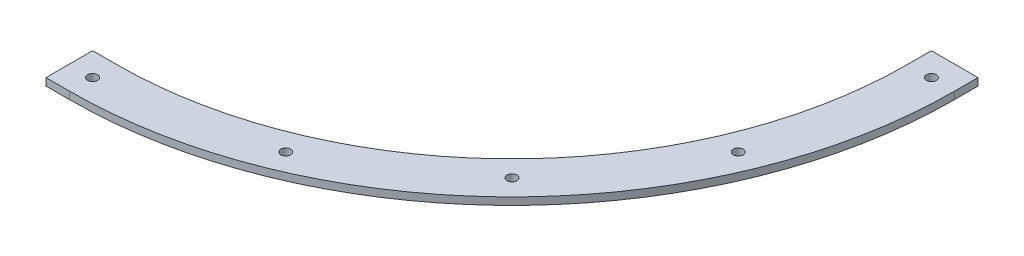
SolidWorks part; units mm, degrees
ref_plane "Front Plane" through (0, 0, 0) normal (0, 0, 1) x (1, 0, 0)
ref_plane "Top Plane" through (0, 0, 0) normal (0, 1, 0) x (1, 0, 0)
ref_plane "Right Plane" through (0, 0, 0) normal (1, 0, 0) x (0, 0, -1)
sketch "Sketch1" plane through (0, 0, 0) normal (0, 1, 0) x (1, 0, 0)
  line L0 (0, -280) -> (100, -280)
  line L1 (100, -280) -> (100, -209.6016)
  line L2 (280, -100) -> (209.6016, -100)
  line L3 (0, 0) -> (0, -280) construction
  line L4 (280, 0) -> (280, -100)
  line L5 (-280, 280) -> (280, 280) construction
  line L6 (-280, 280) -> (-280, -280) construction
  line L7 (-280, -280) -> (280, -280) construction
  line L8 (280, 280) -> (280, -280) construction
  line L9 (-280, 280) -> (280, -280) construction
  line L10 (-280, -280) -> (280, 280) construction
  line L11 (100, -209.6016) -> (209.6016, -100)
  line L12 (-280, 0) -> (-280, -100)
  line L13 (-280, -100) -> (-209.6016, -100)
  line L14 (-209.6016, -100) -> (-100, -209.6016)
  line L15 (-100, -280) -> (-100, -209.6016)
  line L16 (0, -280) -> (-100, -280)
  line L17 (0, 280) -> (-100, 280)
  line L18 (-100, 280) -> (-100, 209.6016)
  line L19 (-100, 209.6016) -> (-209.6016, 100)
  line L20 (-280, 100) -> (-209.6016, 100)
  line L21 (-280, 0) -> (-280, 100)
  line L22 (280, 0) -> (280, 100)
  line L23 (280, 100) -> (209.6016, 100)
  line L24 (209.6016, 100) -> (100, 209.6016)
  line L25 (100, 280) -> (100, 209.6016)
  line L26 (0, 280) -> (100, 280)
  line L27 (111.5258, -219.2889) -> (219.2889, -111.5258) construction
  line L28 (219.2889, -111.5258) -> (247.5732, -139.8101) construction
  line L29 (247.5732, -139.8101) -> (139.8101, -247.5732) construction
  line L30 (139.8101, -247.5732) -> (111.5258, -219.2889) construction
  line L31 (-100, -270) -> (100, -270) construction
  line L32 (-90, -280) -> (-90, 280) construction
  line L33 (-75, -75) -> (75, -75) construction
  line L34 (-75, -75) -> (-75, 75) construction
  line L35 (-75, 75) -> (75, 75) construction
  line L36 (75, -75) -> (75, 75) construction
  line L37 (-75, -75) -> (75, 75) construction
  line L38 (-75, 75) -> (75, -75) construction
  line L39 (-100, -260) -> (100, -260) construction
  line L40 (-280, 40) -> (280, 40) construction
  line L41 (0, 280) -> (0, 0) construction
  line L42 (-280, -90) -> (280, -90) construction
  line L43 (-260, -100) -> (-260, 100) construction
  line L44 (0, 0) -> (-280, 0) construction
  arc A0 (100, -280) -> (280, -100) centre (100, -100) ccw construction
  circle A1 centre (-47.5, -192) radius 2.125
  circle A2 centre (-47.5, -217) radius 2.125
  circle A3 centre (47.5, -217) radius 2.125
  circle A4 centre (47.5, -192) radius 2.125
  circle A5 centre (-192, 47.5) radius 2.125
  circle A6 centre (-217, 47.5) radius 2.125
  circle A7 centre (-192, -47.5) radius 2.125
  circle A8 centre (-217, -47.5) radius 2.125
  circle A9 centre (47.5, 192) radius 2.125
  circle A10 centre (47.5, 217) radius 2.125
  circle A11 centre (-47.5, 192) radius 2.125
  circle A12 centre (-47.5, 217) radius 2.125
  circle A13 centre (192, -47.5) radius 2.125
  circle A14 centre (217, -47.5) radius 2.125
  circle A15 centre (192, 47.5) radius 2.125
  circle A16 centre (217, 47.5) radius 2.125
  circle A17 centre (-90, -270) radius 2.125
  circle A18 centre (-30, -270) radius 2.125
  circle A19 centre (30, -270) radius 2.125
  circle A20 centre (90, -270) radius 2.125
  circle A21 centre (-270, 90) radius 2.125
  circle A22 centre (-270, 30) radius 2.125
  circle A23 centre (-270, -30) radius 2.125
  circle A24 centre (-270, -90) radius 2.125
  circle A25 centre (90, 270) radius 2.125
  circle A26 centre (30, 270) radius 2.125
  circle A27 centre (-30, 270) radius 2.125
  circle A28 centre (-90, 270) radius 2.125
  circle A29 centre (270, -90) radius 2.125
  circle A30 centre (270, -30) radius 2.125
  circle A31 centre (270, 30) radius 2.125
  circle A32 centre (270, 90) radius 2.125
  circle A33 centre (-90, -250) radius 2.125
  circle A34 centre (-90, -180) radius 2.125
  circle A35 centre (-90, -110) radius 2.125
  circle A36 centre (-90, -40) radius 2.125
  circle A37 centre (-90, 30) radius 2.125
  circle A38 centre (-90, 50) radius 2.125
  circle A39 centre (-90, 100) radius 2.125 construction
  circle A40 centre (-90, 150) radius 2.125
  circle A41 centre (-90, 200) radius 2.125 construction
  circle A42 centre (-90, 250) radius 2.125
  circle A43 centre (90, -250) radius 2.125
  circle A44 centre (90, -180) radius 2.125
  circle A45 centre (90, -110) radius 2.125
  circle A46 centre (90, -40) radius 2.125
  circle A47 centre (90, 30) radius 2.125
  circle A48 centre (90, 50) radius 2.125
  circle A49 centre (90, 100) radius 2.125 construction
  circle A50 centre (90, 150) radius 2.125
  circle A51 centre (90, 200) radius 2.125 construction
  circle A52 centre (90, 250) radius 2.125
  circle A53 centre (-250, -90) radius 2.125
  circle A54 centre (-180, -90) radius 2.125
  circle A55 centre (-110, -90) radius 2.125
  circle A56 centre (-110, 90) radius 2.125
  circle A57 centre (-180, 90) radius 2.125
  circle A58 centre (-250, 90) radius 2.125
  circle A59 centre (110, -90) radius 2.125
  circle A60 centre (180, -90) radius 2.125
  circle A61 centre (250, -90) radius 2.125
  circle A62 centre (110, 90) radius 2.125
  circle A63 centre (180, 90) radius 2.125
  circle A64 centre (250, 90) radius 2.125
  point P33 (0, 0)
  point P68 (0, 0)
  point P107 (0, 0)
  dimension "D10" = 25
  dimension "4.25" = 4.25
  dimension "D11" = 4.25
  dimension "D16" = 4.25
  dimension "D24" = 4.25
  dimension "D28" = 4.25
  dimension "D32" = 4.25
  dimension "D1" = 560
  dimension "D2" = 90
  dimension "D3" = 280
  dimension "D4" = 4
  dimension "D5" = 100
  dimension "D6" = 155
  dimension "D7" = 152.4
  dimension "D8" = 15
  dimension "D9" = 40
  dimension "D12" = 47.5
  dimension "D13" = 63
  dimension "D15" = 10
  dimension "D17" = 10
  dimension "D18" = 76.2
  dimension "D19" = 150
  dimension "D20" = 150
  dimension "D23" = 10
  dimension "D25" = 10
  dimension "D26" = 300
  dimension "D29" = 10
  dimension "D31" = 20
  dimension "D33" = 10
  dimension "D21" = 4
  dimension "D27" = 5
  dimension "D30" = 5
  dimension "D34" = 3
  dimension "D14" = 4
  dimension "D22" = 4
extrude "Boss-Extrude1" add sketch "Sketch1" along normal blind 3.175 contours L26 L17 L18 L19 L20 L21 L12 L13 L14 L15 L16 L0 L1 L11 L2 L4 L22 L23 L24 L25 region at (0, 0, -0.0137)
sketch "Sketch2" plane through (0, 3.175, 0) normal (0, 1, 0) x (1, 0, 0)
  line L11 (80, -260) -> (100, -260)
  line L12 (80, -260) -> (80, -280)
  line L13 (80, -280) -> (93.1985, -280) construction
  line L14 (100, -260) -> (100, -280) construction
  line L15 (80, -260) -> (100, -280) construction
  line L16 (80, -280) -> (100, -260) construction
  line L17 (260, -80) -> (280, -80)
  line L18 (260, -80) -> (260, -100)
  line L19 (260, -100) -> (280, -100) construction
  line L20 (280, -80) -> (280, -100) construction
  line L21 (260, -80) -> (280, -100) construction
  line L22 (260, -100) -> (280, -80) construction
  line L38 (100, 280) -> (-100, 280)
  line L39 (-100, 280) -> (-100, 209.6016)
  line L40 (-100, 209.6016) -> (-209.6016, 100)
  line L41 (-209.6016, 100) -> (-280, 100)
  line L42 (-280, 100) -> (-280, -100)
  line L43 (-280, -100) -> (-209.6016, -100)
  line L44 (-209.6016, -100) -> (-100, -209.6016)
  line L45 (-100, -209.6016) -> (-100, -280)
  line L46 (-100, -280) -> (100, -280)
  line L47 (100, -280) -> (100, -209.6016)
  line L48 (100, -209.6016) -> (209.6016, -100)
  line L49 (209.6016, -100) -> (280, -100)
  line L50 (280, -100) -> (280, 100)
  line L51 (280, 100) -> (209.6016, 100)
  line L52 (209.6016, 100) -> (100, 209.6016)
  line L53 (100, 209.6016) -> (100, 280)
  line L54 (100, 280) -> (-100, 280)
  line L55 (-100, 280) -> (-100, 209.6016)
  line L56 (-100, 209.6016) -> (-209.6016, 100)
  line L57 (-209.6016, 100) -> (-280, 100)
  line L58 (-280, 100) -> (-280, -100)
  line L59 (-280, -100) -> (-209.6016, -100)
  line L60 (-209.6016, -100) -> (-100, -209.6016)
  line L61 (-100, -209.6016) -> (-100, -280)
  line L62 (-100, -280) -> (80, -280)
  line L63 (100, -260) -> (100, -209.6016)
  line L64 (100, -209.6016) -> (209.6016, -100)
  line L65 (209.6016, -100) -> (260, -100)
  line L66 (280, -80) -> (280, 100)
  line L67 (280, 100) -> (209.6016, 100)
  line L68 (209.6016, 100) -> (100, 209.6016)
  line L69 (100, 209.6016) -> (100, 280)
  point P0 (90, -270)
  point P5 (270, -90)
  dimension "D1" = 0
extrude "Cut-Extrude1" cut sketch "Sketch2" against normal through all
sketch "Sketch3" plane through (0, 3.175, 0) normal (0, 1, 0) x (1, 0, 0)
  line L0 (260, -90) -> (267.875, -90)
  line L1 (272.125, -90) -> (280, -90)
  line L2 (90, -260) -> (90, -267.875)
  line L3 (90, -280) -> (90, -272.125)
  arc A0 (90, -270) -> (270, -90) centre (90, -90) ccw construction
  arc A1 (90, -280) -> (280, -90) centre (90, -90) ccw
  arc A2 (90, -260) -> (260, -90) centre (90, -90) ccw
  circle A3 centre (270, -90) radius 2.125 construction
  circle A4 centre (90, -270) radius 2.125 construction
  arc A5 (267.875, -90) -> (272.125, -90) centre (270, -90) ccw
  arc A6 (90, -272.125) -> (90, -267.875) centre (90, -270) ccw
  point P11 (0, 0)
  dimension "D1" = 10
  dimension "D2" = 10
extrude "Boss-Extrude2" add sketch "Sketch3" against normal up to surface (3.175 mm away) up to face at (90, 0, 272.125)
sketch "Sketch4" plane through (0, 3.175, 0) normal (0, 1, 0) x (1, 0, 0)
  line L0 (90, -90) -> (217.2792, -217.2792) construction
  line L1 (100, -280) -> (100, -279.7367) construction
  line L2 (100, -280) -> (80, -280) construction
  line L3 (100, -280) -> (90, -280)
  line L4 (100, -280) -> (100, -279.7367)
  line L7 (279.7367, -100) -> (284.4157, -100)
  line L8 (284.4157, -100) -> (280, -90)
  arc A0 (90, -270) -> (270, -90) centre (90, -90) ccw construction
  arc A1 (90, -270) -> (270, -90) centre (90, -90) ccw construction
  circle A2 centre (217.2792, -217.2792) radius 2.125
  circle A3 centre (256.2075, -159.102) radius 2.125
  circle A4 centre (159.102, -256.2075) radius 2.125
  arc A5 (90, -280) -> (280, -90) centre (90, -90) ccw construction
  arc A6 (90, -280) -> (100, -279.7367) centre (90, -90) ccw
  arc A7 (280, -90) -> (279.7367, -100) centre (90, -90) cw
  dimension "D1" = 4.25
  dimension "D2" = 4.25
  dimension "D3" = 70
extrude "Cut-Extrude2" cut sketch "Sketch4" against normal through all
